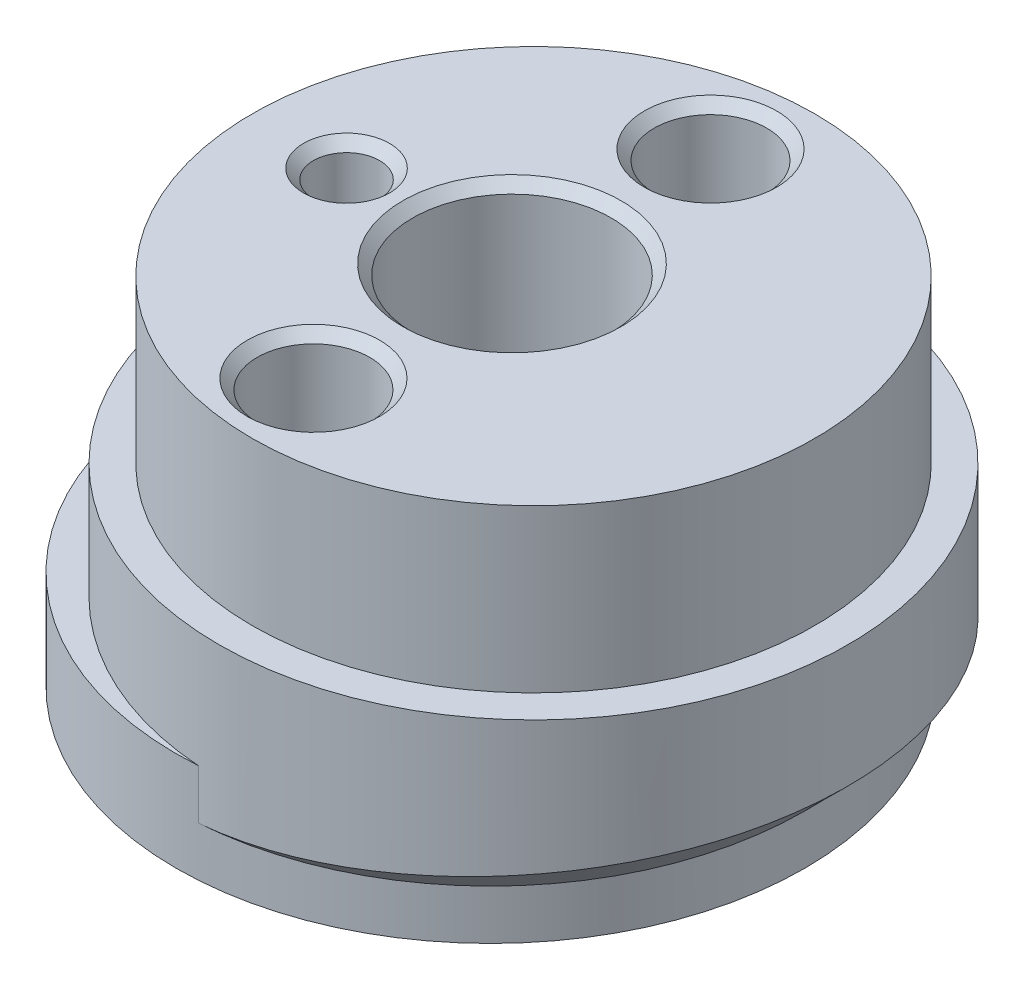
SolidWorks part; units mm, degrees
ref_plane "Front Plane" through (0, 0, 0) normal (0, 0, 1) x (1, 0, 0)
ref_plane "Top Plane" through (0, 0, 0) normal (0, 1, 0) x (1, 0, 0)
ref_plane "Right Plane" through (0, 0, 0) normal (1, 0, 0) x (0, 0, -1)
sketch "Sketch1" plane through (0, 0, 0) normal (0, 1, 0) x (1, 0, 0)
  circle A0 centre (0, 0) radius 3
  circle A2 centre (-0.65, 0) radius 9.5
  dimension "D1" = 6
  dimension "D2" = 19
  dimension "D3" = 0.65
extrude "Boss-Extrude1" add sketch "Sketch1" along normal blind 3
sketch "Sketch7" plane through (0, 3, 0) normal (0, 1, 0) x (1, 0, 0)
  circle A0 centre (0.65, 0) radius 8.5
  circle A1 centre (0, 0) radius 3 construction
  circle A2 centre (0, 0) radius 3
  dimension "D1" = 17
  dimension "D2" = 0.65
extrude "Boss-Extrude5" add sketch "Sketch7" along normal blind 8.4
sketch "Sketch8" plane through (0, 3, 0) normal (0, 1, 0) x (1, 0, 0)
  circle A0 centre (0.65, 0) radius 8.5 construction
  circle A1 centre (0.65, 0) radius 8.5
  circle A2 centre (0.65, 0) radius 9.5
  dimension "D1" = 19
extrude "Boss-Extrude6" add sketch "Sketch8" along normal blind 3.5
chamfer "Chamfer1" distance 1.5 angle 45 1 edges at (8.85, 3, 0)
sketch "Sketch12" plane through (0, 11.4, 0) normal (0, 1, 0) x (1, 0, 0)
  circle A0 centre (0.65, 0) radius 8.5 construction
  circle A1 centre (0, 0) radius 3 construction
  circle A2 centre (0.65, 0) radius 8.5 construction
  circle A3 centre (0, 0) radius 3
  circle A4 centre (-5, 0) radius 1
  dimension "D1" = 2
  dimension "D2" = 5
extrude "Cut-Extrude4" cut sketch "Sketch12" against normal through all
hole_wizard "M3 Clearance Hole1" positions "Sketch11" profile "Sketch10" hole size "M3" standard "DIN" end condition through all
sketch "Sketch11" plane through (0, 11.4, 0) normal (0, 1, 0) x (1, 0, 0)
  circle A0 centre (0, 0) radius 3 construction
  circle A1 centre (0, 0) radius 3
  circle A2 centre (0, 0) radius 6
  point P58 (0, 6)
  point P60 (0, -6)
  dimension "D1" = 12
sketch "Sketch10" plane through (0, 11.4, -6) normal (1, 0, 0) x (0, 0, 1)
  line L0 (0, 0) -> (0, 11.4)
  line L1 (0, 11.4) -> (1.7, 11.4)
  line L2 (1.7, 11.4) -> (1.7, 0)
  line L5 (1.7, 0) -> (0, 0)
  line L11 (0, -6.35) -> (0, 107.95) construction
  dimension "Thru Hole Dia." = 3.4
  dimension "Thru Hole Depth" = 11.4
chamfer "Chamfer2" distance 0.3 angle 45 8 edges at (0, 11.4, 7.7) (0, 11.4, -4.3) (0, 11.4, 3) (-5, 11.4, 1) (0, 0, -4.3) (-5, 0, 1) (0, 0, 7.7) (0, 0, 3)
